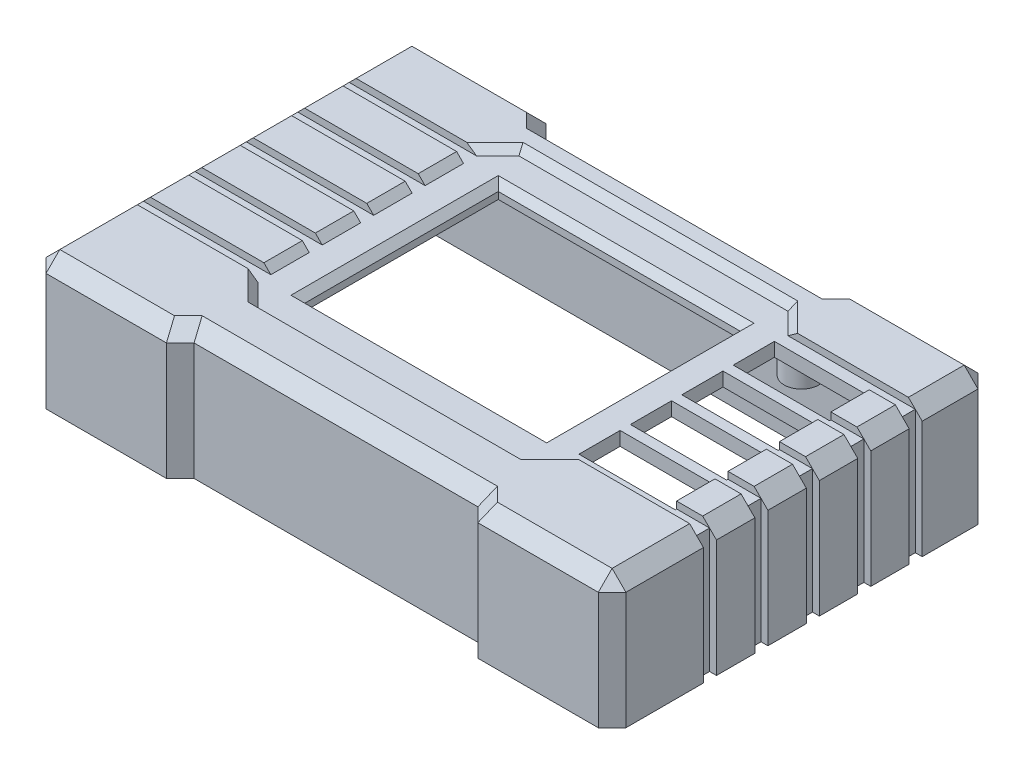
SolidWorks part; units mm, degrees
ref_plane "Спереди" through (0, 0, 0) normal (0, 0, 1) x (1, 0, 0)
ref_plane "Сверху" through (0, 0, 0) normal (0, 1, 0) x (1, 0, 0)
ref_plane "Справа" through (0, 0, 0) normal (1, 0, 0) x (0, 0, -1)
sketch "Эскиз1" plane through (0, 0, 0) normal (0, 1, 0) x (1, 0, 0)
  line L5 (-34.58, 1.516) -> (21.72, 1.516) construction
  line L6 (-37, -22.5) -> (37, -22.5)
  line L9 (-37, -22.5) -> (-37, 22.5)
  line L14 (-37, 22.5) -> (37, 22.5)
  line L15 (37, -22.5) -> (37, 22.5)
  line L20 (-37, -22.5) -> (37, 22.5) construction
  line L21 (-37, 22.5) -> (37, -22.5) construction
  line L34 (17.52, 15.531) -> (36.3729, 15.531) construction
  line L35 (26, 15) -> (32.5, 15) construction
  line L36 (-34.58, -17.984) -> (21.72, -17.984) construction
  line L37 (-34.58, -17.984) -> (-34.58, 21.016) construction
  line L38 (-34.58, 21.016) -> (21.72, 21.016) construction
  line L39 (21.72, -17.984) -> (21.72, 21.016) construction
  line L40 (-34.58, -17.984) -> (21.72, 21.016) construction
  line L41 (-34.58, 21.016) -> (21.72, -17.984) construction
  line L42 (-17.52, 15.531) -> (17.52, 15.531)
  line L47 (-17.52, 15.531) -> (-17.52, -12.499)
  line L48 (-17.52, -12.499) -> (17.52, -12.499)
  line L49 (17.52, 15.531) -> (17.52, -12.499)
  line L50 (-17.52, 15.531) -> (17.52, -12.499) construction
  line L51 (-17.52, -12.499) -> (17.52, 15.531) construction
  line L52 (-56.0698, 1.516) -> (114.5698, 1.516) construction
  line L53 (26, 15) -> (26, 10.5) construction
  line L54 (26, 10.5) -> (32.5, 10.5) construction
  line L55 (32.5, 15) -> (32.5, 10.5) construction
  line L56 (26, 7.55) -> (32.5, 7.55) construction
  line L57 (26, 7.55) -> (26, 3.05) construction
  line L58 (26, 3.05) -> (32.5, 3.05) construction
  line L59 (32.5, 7.55) -> (32.5, 3.05) construction
  line L60 (26, 0.1) -> (32.5, 0.1) construction
  line L61 (26, 0.1) -> (26, -4.4) construction
  line L62 (26, -4.4) -> (32.5, -4.4) construction
  line L63 (32.5, 0.1) -> (32.5, -4.4) construction
  line L64 (25.931, -7.35) -> (32.431, -7.35) construction
  line L65 (25.931, -7.35) -> (25.931, -11.85) construction
  line L66 (25.931, -11.85) -> (32.431, -11.85) construction
  line L67 (32.431, -7.35) -> (32.431, -11.85) construction
  line L72 (26, 15) -> (32.5, 10.5) construction
  line L74 (26, 10.5) -> (32.5, 15) construction
  line L75 (26, 0.1) -> (32.5, -4.4) construction
  line L76 (36.022, 9.969) -> (22.478, 9.969)
  line L77 (36.022, 9.969) -> (36.022, 15.531)
  line L78 (36.022, 15.531) -> (22.478, 15.531)
  line L79 (22.478, 9.969) -> (22.478, 15.531)
  line L80 (36.022, 9.969) -> (22.478, 15.531) construction
  line L81 (36.022, 15.531) -> (22.478, 9.969) construction
  line L82 (26, -4.4) -> (32.5, 0.1) construction
  line L83 (26.069, -7.35) -> (32.431, -11.85) construction
  line L84 (32.431, -7.35) -> (25.931, -11.85) construction
  line L85 (26, 7.55) -> (32.5, 3.05) construction
  line L86 (32.5, 7.55) -> (26, 3.05) construction
  line L87 (0, 22.5) -> (0, -22.5) construction
  line L88 (36.022, 2.519) -> (22.478, 2.519)
  line L89 (36.022, 2.519) -> (36.022, 8.081)
  line L90 (36.022, 8.081) -> (22.478, 8.081)
  line L91 (22.478, 2.519) -> (22.478, 8.081)
  line L92 (36.022, 2.519) -> (22.478, 8.081) construction
  line L93 (36.022, 8.081) -> (22.478, 2.519) construction
  line L94 (36.022, -4.931) -> (22.478, -4.931)
  line L95 (36.022, -4.931) -> (36.022, 0.631)
  line L96 (36.022, 0.631) -> (22.478, 0.631)
  line L97 (22.478, -4.931) -> (22.478, 0.631)
  line L98 (36.022, -4.931) -> (22.478, 0.631) construction
  line L99 (36.022, 0.631) -> (22.478, -4.931) construction
  line L100 (36.022, -12.381) -> (22.478, -12.381)
  line L101 (36.022, -12.381) -> (36.022, -6.819)
  line L102 (36.022, -6.819) -> (22.478, -6.819)
  line L103 (22.478, -12.381) -> (22.478, -6.819)
  line L104 (36.022, -12.381) -> (22.478, -6.819) construction
  line L105 (36.022, -6.819) -> (22.478, -12.381) construction
  line L106 (-36.022, -6.819) -> (-22.478, -12.381) construction
  line L107 (-36.022, -12.381) -> (-22.478, -6.819) construction
  line L108 (-36.022, 0.631) -> (-22.478, -4.931) construction
  line L109 (-36.022, -4.931) -> (-22.478, 0.631) construction
  line L110 (-36.022, 8.081) -> (-22.478, 2.519) construction
  line L111 (-36.022, 2.519) -> (-22.478, 8.081) construction
  line L112 (-32.5, 7.55) -> (-26, 3.05) construction
  line L113 (-26, 7.55) -> (-32.5, 3.05) construction
  line L114 (-32.431, -7.35) -> (-25.931, -11.85) construction
  line L115 (-26.069, -7.35) -> (-32.431, -11.85) construction
  line L116 (-26, -4.4) -> (-32.5, 0.1) construction
  line L117 (-36.022, 15.531) -> (-22.478, 9.969) construction
  line L118 (-36.022, 9.969) -> (-22.478, 15.531) construction
  line L119 (-26, 0.1) -> (-32.5, -4.4) construction
  line L120 (-26, 10.5) -> (-32.5, 15) construction
  line L121 (-26, 15) -> (-32.5, 10.5) construction
  line L122 (-32.431, -7.35) -> (-32.431, -11.85) construction
  line L123 (-25.931, -11.85) -> (-32.431, -11.85) construction
  line L124 (-25.931, -7.35) -> (-25.931, -11.85) construction
  line L125 (-25.931, -7.35) -> (-32.431, -7.35) construction
  line L126 (-32.5, 0.1) -> (-32.5, -4.4) construction
  line L127 (-26, -4.4) -> (-32.5, -4.4) construction
  line L128 (-26, 0.1) -> (-26, -4.4) construction
  line L129 (-26, 0.1) -> (-32.5, 0.1) construction
  line L130 (-32.5, 7.55) -> (-32.5, 3.05) construction
  line L131 (-26, 3.05) -> (-32.5, 3.05) construction
  line L132 (-26, 7.55) -> (-26, 3.05) construction
  line L133 (-26, 7.55) -> (-32.5, 7.55) construction
  line L134 (-32.5, 15) -> (-32.5, 10.5) construction
  line L135 (-26, 10.5) -> (-32.5, 10.5) construction
  line L136 (-26, 15) -> (-26, 10.5) construction
  line L137 (-26, 15) -> (-32.5, 15) construction
  line L138 (-22.478, -12.381) -> (-22.478, -6.819) construction
  line L139 (-36.022, -6.819) -> (-22.478, -6.819) construction
  line L140 (-36.022, -12.381) -> (-36.022, -6.819) construction
  line L141 (-36.022, -12.381) -> (-22.478, -12.381) construction
  line L142 (-22.478, -4.931) -> (-22.478, 0.631) construction
  line L143 (-36.022, 0.631) -> (-22.478, 0.631) construction
  line L144 (-36.022, -4.931) -> (-36.022, 0.631) construction
  line L145 (-36.022, -4.931) -> (-22.478, -4.931) construction
  line L146 (-22.478, 2.519) -> (-22.478, 8.081) construction
  line L147 (-36.022, 8.081) -> (-22.478, 8.081) construction
  line L148 (-36.022, 2.519) -> (-36.022, 8.081) construction
  line L149 (-36.022, 2.519) -> (-22.478, 2.519) construction
  line L150 (-22.478, 9.969) -> (-22.478, 15.531) construction
  line L151 (-36.022, 15.531) -> (-22.478, 15.531) construction
  line L152 (-36.022, 9.969) -> (-36.022, 15.531) construction
  line L153 (-36.022, 9.969) -> (-22.478, 9.969) construction
  line L154 (22.478, 15.531) -> (22.478, -16.6587) construction
  point P0 (0, 0)
  point P10 (-6.43, 1.516)
  point P17 (0, 1.516)
  point P36 (29.25, 12.75)
  point P42 (29.25, 5.3)
  point P48 (29.25, -2.15)
  point P53 (29.25, -9.6)
  point P95 (-29.25, -9.6)
  point P96 (-29.25, -2.15)
  point P97 (-29.25, 5.3)
  point P98 (-29.25, 12.75)
  dimension "D6" = 4.5
  dimension "D1" = 74
  dimension "D2" = 45
  dimension "D3" = 7.5
  dimension "D4" = 4.5
  dimension "D5" = 6.5
  dimension "D7" = 56.3
  dimension "D8" = 39
  dimension "D9" = 28.03
  dimension "D10" = 35.04
  dimension "D11" = 2.95
  dimension "D12" = 2.95
  dimension "D13" = 2.95
  dimension "D14" = 13.544
  dimension "D15" = 4.2
  dimension "D16" = 0.978
  dimension "D17" = 22.35
extrude "Бобышка-Вытянуть1" add sketch "Эскиз1" along normal blind 2
sketch "Эскиз2" plane through (-37, 0, 0) normal (-1, 0, 0) x (0, 0, 1)
  line L0 (22.5, 2) -> (22.5, 0) construction
  line L1 (-22.5, 2) -> (22.5, 2)
  line L2 (-22.5, 2) -> (-22.5, -16)
  line L3 (-22.5, -16) -> (22.5, -16)
  line L4 (22.5, 2) -> (22.5, -16)
  dimension "D1" = 18
extrude "Бобышка-Вытянуть2" add sketch "Эскиз2" along normal blind 4
sketch "Эскиз3" plane through (37, 0, 0) normal (1, 0, 0) x (0, 0, -1)
  line L1 (-22.5, 2) -> (22.5, 2)
  line L2 (-22.5, 2) -> (-22.5, -16)
  line L3 (-22.5, -16) -> (22.5, -16)
  line L4 (22.5, 2) -> (22.5, -16)
extrude "Бобышка-Вытянуть3" add sketch "Эскиз3" along normal blind 4
sketch "Эскиз4" plane through (0, 0, -22.5) normal (0, 0, -1) x (-1, 0, 0)
  line L1 (-41, 2) -> (41, 2)
  line L2 (-41, 2) -> (-41, -16)
  line L3 (-41, -16) -> (41, -16)
  line L4 (41, 2) -> (41, -16)
extrude "Бобышка-Вытянуть4" add sketch "Эскиз4" along normal blind 3
sketch "Эскиз5" plane through (0, 0, 22.5) normal (0, 0, 1) x (1, 0, 0)
  line L1 (-41, 2) -> (41, 2)
  line L2 (-41, 2) -> (-41, -16)
  line L3 (-41, -16) -> (41, -16)
  line L4 (41, 2) -> (41, -16)
extrude "Бобышка-Вытянуть5" add sketch "Эскиз5" along normal blind 3
sketch "Эскиз7" plane through (0, 2, 0) normal (0, 1, 0) x (1, 0, 0)
  line L0 (-17.52, 15.531) -> (-17.52, -12.499) construction
  line L17 (-41, -25.5) -> (-41, 25.5) construction
  line L18 (36.022, 15.531) -> (36.022, 9.969)
  line L51 (36.022, 15.531) -> (41, 15.531)
  line L52 (36.022, 9.969) -> (41, 9.969)
  line L53 (-41, -6.819) -> (-41, -12.381)
  line L54 (-22.5537, -12.381) -> (-41, -12.381)
  line L55 (-22.5537, -6.819) -> (-22.5537, -12.381)
  line L56 (-22.5537, -6.819) -> (-41, -6.819)
  line L57 (-41, 0.631) -> (-41, -4.931)
  line L58 (-22.5537, -4.931) -> (-41, -4.931)
  line L59 (-22.5537, 0.631) -> (-22.5537, -4.931)
  line L60 (-22.5537, 0.631) -> (-41, 0.631)
  line L61 (-41, 8.081) -> (-41, 2.519)
  line L62 (-22.5537, 2.519) -> (-41, 2.519)
  line L63 (-22.5537, 8.081) -> (-22.5537, 2.519)
  line L64 (-22.5537, 8.081) -> (-41, 8.081)
  line L65 (-41, 15.531) -> (-41, 9.969)
  line L66 (-22.5537, 9.969) -> (-41, 9.969)
  line L67 (-22.5537, 15.531) -> (-22.5537, 9.969)
  line L68 (-22.5537, 15.531) -> (-41, 15.531)
  line L69 (41, 15.531) -> (41, 9.969)
  line L70 (36.022, 8.081) -> (36.022, 2.519)
  line L71 (36.022, 8.081) -> (41, 8.081)
  line L72 (36.022, 2.519) -> (41, 2.519)
  line L73 (41, 8.081) -> (41, 2.519)
  line L74 (-22.5537, 15.531) -> (-22.5537, 17.419) construction
  line L75 (36.022, 2.519) -> (36.022, 8.081) construction
  line L76 (36.022, 0.631) -> (36.022, -4.931)
  line L77 (36.022, 0.631) -> (41, 0.631)
  line L78 (36.022, -4.931) -> (41, -4.931)
  line L79 (41, 0.631) -> (41, -4.931)
  line L80 (36.022, -6.819) -> (36.022, -12.381)
  line L81 (36.022, -6.819) -> (41, -6.819)
  line L82 (36.022, -12.381) -> (41, -12.381)
  line L83 (41, -6.819) -> (41, -12.381)
  line L84 (41, 25.5) -> (41, -25.5) construction
  line L85 (-41, -25.5) -> (-22.5537, -25.5)
  line L86 (-41, -25.5) -> (-41, -14.269)
  line L87 (-41, -14.269) -> (-22.5537, -14.269)
  line L88 (-22.5537, -25.5) -> (-22.5537, -14.269) construction
  line L89 (41, -25.5) -> (22.5537, -25.5)
  line L90 (41, -25.5) -> (41, -14.269)
  line L91 (41, -14.269) -> (22.5537, -14.269)
  line L92 (22.5537, -25.5) -> (22.5537, -14.269) construction
  line L97 (-41, 25.5) -> (41, 25.5) construction
  line L98 (-22.5537, 17.419) -> (-41, 17.419)
  line L115 (22.478, -2.15) -> (17.52, -2.15) construction
  line L116 (-41, 25.5) -> (-22.5537, 25.5)
  line L120 (41, 25.5) -> (22.5537, 25.5)
  line L124 (-22.5537, -25.5) -> (22.5537, -25.5)
  line L125 (-22.5537, -25.5) -> (-22.5537, -17.457) construction
  line L126 (-22.5537, -17.457) -> (22.5537, -17.457) construction
  line L127 (22.5537, -25.5) -> (22.5537, -17.457) construction
  line L128 (22.478, 0.631) -> (22.478, -4.931) construction
  line L129 (17.52, -12.499) -> (17.52, 15.531) construction
  line L130 (0, -12.499) -> (0, -17.457) construction
  line L131 (-17.52, -12.499) -> (17.52, -12.499) construction
  line L132 (-22.5537, -14.269) -> (-19.3657, -17.457)
  line L133 (22.5537, -14.269) -> (19.3657, -17.457)
  line L134 (-19.3657, -17.457) -> (19.3657, -17.457)
  line L135 (36.022, -6.819) -> (22.478, -6.819) construction
  line L136 (-22.5537, -12.381) -> (-22.5537, -14.269) construction
  line L137 (-22.5537, 20.489) -> (22.5537, 20.489) construction
  line L138 (-10.3983, 20.489) -> (-10.3983, 15.531) construction
  line L139 (17.52, 15.531) -> (-17.52, 15.531) construction
  line L142 (-22.5537, 25.5) -> (22.5537, 25.5)
  line L144 (-41, 25.5) -> (-41, 17.419)
  line L145 (41, 25.5) -> (41, 17.419)
  line L146 (41, 17.419) -> (22.5537, 17.419)
  line L147 (-22.5537, 17.419) -> (-19.4836, 20.489)
  line L148 (22.5537, 17.419) -> (19.4836, 20.489)
  line L150 (-22.5537, 17.419) -> (-22.5537, 25.5) construction
  line L151 (22.5537, 17.419) -> (22.5537, 25.5) construction
  line L152 (-19.4836, 20.489) -> (19.4836, 20.489)
  line L153 (36.022, 15.531) -> (22.478, 15.531) construction
  line L154 (22.478, 9.969) -> (36.022, 9.969) construction
  line L155 (36.022, 8.081) -> (22.478, 8.081) construction
  line L156 (22.478, 2.519) -> (36.022, 2.519) construction
  line L157 (36.022, 0.631) -> (22.478, 0.631) construction
  line L158 (22.478, -4.931) -> (36.022, -4.931) construction
  line L161 (22.478, -12.381) -> (36.022, -12.381) construction
  line L162 (-22.5537, 9.969) -> (-22.5537, 8.081) construction
  dimension "D1" = 5.0337
  dimension "D2" = 45
  dimension "D3" = 45
  dimension "D4" = 5.562
  dimension "D5" = 45
  dimension "D6" = 45
extrude "Бобышка-Вытянуть6" add sketch "Эскиз7" along normal blind 1
sketch "Эскиз8" plane through (-41, 0, 0) normal (-1, 0, 0) x (0, 0, 1)
  line L0 (-25.5, -16) -> (25.5, -16) construction
  line L1 (-15.531, 3) -> (-9.969, 3)
  line L2 (-15.531, 3) -> (-15.531, -16)
  line L3 (-15.531, -16) -> (-9.969, -16)
  line L4 (-9.969, 3) -> (-9.969, -16)
  line L5 (-15.531, 3) -> (-9.969, 3) construction
  line L6 (14.269, 3) -> (25.5, 3)
  line L7 (-8.081, 3) -> (-2.519, 3)
  line L8 (-8.081, 3) -> (-8.081, -16)
  line L9 (-8.081, -16) -> (-2.519, -16)
  line L10 (-2.519, 3) -> (-2.519, -16)
  line L11 (-0.631, 3) -> (4.931, 3)
  line L12 (-0.631, 3) -> (-0.631, -16)
  line L13 (-0.631, -16) -> (4.931, -16)
  line L14 (4.931, 3) -> (4.931, -16)
  line L15 (6.819, 3) -> (12.381, 3)
  line L16 (6.819, 3) -> (6.819, -16)
  line L17 (6.819, -16) -> (12.381, -16)
  line L18 (12.381, 3) -> (12.381, -16)
  line L19 (14.269, 3) -> (14.269, -16)
  line L20 (25.5, 3) -> (25.5, -16)
  line L21 (14.269, -16) -> (25.5, -16)
  line L26 (-17.419, 3) -> (-25.5, 3)
  line L27 (-17.419, 3) -> (-17.419, -16)
  line L28 (-25.5, 3) -> (-25.5, -16)
  line L29 (-17.419, -16) -> (-25.5, -16)
  line L30 (25.5, -16) -> (-25.5, -16) construction
extrude "Бобышка-Вытянуть7" add sketch "Эскиз8" along normal blind 1
sketch "Эскиз9" plane through (41, 0, 0) normal (1, 0, 0) x (0, 0, -1)
  line L0 (-25.5, -16) -> (25.5, -16) construction
  line L1 (-12.381, 3) -> (-6.819, 3)
  line L2 (-12.381, 3) -> (-12.381, -16)
  line L3 (-12.381, -16) -> (-6.819, -16)
  line L4 (-6.819, 3) -> (-6.819, -16)
  line L5 (-12.381, 3) -> (-6.819, 3) construction
  line L6 (-14.269, 3) -> (-25.5, 3)
  line L7 (-4.931, 3) -> (0.631, 3)
  line L8 (-4.931, 3) -> (-4.931, -16)
  line L9 (-4.931, -16) -> (0.631, -16)
  line L10 (0.631, 3) -> (0.631, -16)
  line L11 (2.519, 3) -> (8.081, 3)
  line L12 (2.519, 3) -> (2.519, -16)
  line L13 (2.519, -16) -> (8.081, -16)
  line L14 (8.081, 3) -> (8.081, -16)
  line L15 (9.969, 3) -> (15.531, 3)
  line L16 (9.969, 3) -> (9.969, -16)
  line L17 (9.969, -16) -> (15.531, -16)
  line L18 (15.531, 3) -> (15.531, -16)
  line L19 (-14.269, 3) -> (-14.269, -16)
  line L20 (-25.5, 3) -> (-25.5, -16)
  line L21 (-14.269, -16) -> (-25.5, -16)
  line L26 (17.419, 3) -> (25.5, 3)
  line L27 (17.419, 3) -> (17.419, -16)
  line L28 (25.5, 3) -> (25.5, -16)
  line L29 (17.419, -16) -> (25.5, -16)
extrude "Бобышка-Вытянуть8" add sketch "Эскиз9" along normal blind 1
sketch "Эскиз11" plane through (0, 3, 0) normal (0, 1, 0) x (1, 0, 0)
  line L0 (-42, 25.5) -> (-42, 27.5)
  line L1 (-42, -25.5) -> (-42, -27.5)
  line L2 (42, 25.5) -> (42, 27.5)
  line L3 (42, -25.5) -> (42, -27.5)
  line L4 (42, -27.5) -> (22.5537, -27.5)
  line L5 (-42, -27.5) -> (-22.5537, -27.5)
  line L7 (-42, 27.5) -> (-22.5537, 27.5)
  line L8 (42, 27.5) -> (22.5537, 27.5)
  line L10 (-42, 17.419) -> (-42, 25.5) construction
  line L11 (-22.5537, 17.419) -> (-22.5537, 27.5) construction
  line L13 (42, 25.5) -> (-42, 25.5) construction
  line L14 (-22.5537, 27.5) -> (-20.5537, 25.5)
  line L15 (-20.5537, 25.5) -> (-42, 25.5)
  line L17 (22.5537, 27.5) -> (20.5537, 25.5)
  line L20 (42, 25.5) -> (20.5537, 25.5)
  line L21 (-22.5537, -27.5) -> (-20.5537, -25.5)
  line L22 (-42, -25.5) -> (42, -25.5) construction
  line L23 (-20.5537, -25.5) -> (-42, -25.5)
  line L24 (22.5537, -27.5) -> (20.5537, -25.5)
  line L25 (20.5537, -25.5) -> (42, -25.5)
  dimension "D1" = 2
  dimension "D2" = 45
  dimension "D3" = 45
  dimension "D4" = 45
  dimension "D5" = 45
extrude "Бобышка-Вытянуть9" add sketch "Эскиз11" against normal up to vertex (19 mm away) up to point (42, -16, 25.5)
chamfer "Фаска15" distance 2 angle 45 26 edges at (42, 3, -12.75) (42, 3, -5.3) (42, 3, 2.15) (42, 3, 9.6) (42, 3, 20.8845) (42, -6.5, 27.5) (32.2768, 3, 27.5) (21.5537, 3, 26.5) (0, 3, 25.5) (-21.5537, 3, 26.5) (-32.2768, 3, 27.5) (-42, -6.5, 27.5) (-42, 3, 20.8845) (-42, 3, 9.6) (-42, 3, 2.15) (-42, 3, -5.3) (-42, 3, -12.75) (42, -6.5, -27.5) (42, 3, -22.4595) (32.2768, 3, -27.5) (21.5537, 3, -26.5) (0, 3, -25.5) (-21.5537, 3, -26.5) (-42, 3, -22.4595) (-32.2768, 3, -27.5) (-42, -6.5, -27.5)
chamfer "Фаска16" distance 1 angle 45 10 edges at (20.9597, 3, 15.863) (0, 3, 17.457) (-20.9597, 3, 15.863) (-22.5537, 3, 9.6) (-22.5537, 3, 2.15) (-22.5537, 3, -5.3) (-22.5537, 3, -12.75) (21.0187, 3, -18.954) (0, 3, -20.489) (-21.0187, 3, -18.954)
sketch "Эскиз12" plane through (0, 0, 0) normal (0, -1, 0) x (1, 0, 0)
  line L0 (-17.52, 12.499) -> (17.52, -15.531) construction
  line L1 (-17.52, 12.499) -> (17.52, 12.499) construction
  line L2 (-17.52, 12.499) -> (-17.52, -15.531) construction
  line L3 (-17.52, -15.531) -> (17.52, -15.531) construction
  line L4 (17.52, 12.499) -> (17.52, -15.531) construction
  line L5 (17.52, 12.499) -> (-17.52, -15.531) construction
  line L6 (-17.52, -1.516) -> (17.52, -1.516) construction
  line L7 (-30.78, 17.984) -> (25.52, 17.984) construction
  line L8 (-30.78, 17.984) -> (-30.78, -21.016) construction
  line L9 (-30.78, -21.016) -> (25.52, -21.016) construction
  line L10 (25.52, 17.984) -> (25.52, -21.016) construction
  line L11 (-30.78, 17.984) -> (25.52, -21.016) construction
  line L12 (25.52, 17.984) -> (-30.78, -21.016) construction
  line L13 (0, 0) -> (0, -1.516) construction
  line L14 (23.22, -18.716) -> (-28.48, -18.716) construction
  line L15 (23.22, -18.716) -> (23.22, 15.684) construction
  line L16 (23.22, 15.684) -> (-28.48, 15.684) construction
  line L17 (-28.48, -18.716) -> (-28.48, 15.684) construction
  line L18 (23.22, -18.716) -> (-28.48, 15.684) construction
  line L19 (23.22, 15.684) -> (-28.48, -18.716) construction
  line L20 (20.35, -18.516) -> (-25.698, -18.516) construction
  line L21 (20.35, -18.516) -> (20.35, 15.484) construction
  line L22 (20.35, 15.484) -> (-25.698, 15.484) construction
  line L23 (-25.698, -18.516) -> (-25.698, 15.484) construction
  line L24 (20.35, -18.516) -> (-25.698, 15.484) construction
  line L25 (20.35, 15.484) -> (-25.698, -18.516) construction
  circle A0 centre (-28.48, 15.684) radius 0.9
  circle A1 centre (-28.48, 15.684) radius 2.5
  circle A2 centre (23.22, 15.684) radius 0.9
  circle A3 centre (23.22, 15.684) radius 2.5
  circle A4 centre (-28.48, -18.716) radius 0.9
  circle A5 centre (-28.48, -18.716) radius 2.5
  circle A6 centre (23.22, -18.716) radius 0.9
  circle A7 centre (23.22, -18.716) radius 2.5
  point P12 (25.52, -1.516)
  point P13 (-2.63, -1.516)
  point P26 (-2.674, -1.516)
  dimension "D6" = 1.8
  dimension "D7" = 5
  dimension "D8" = 2.83
  dimension "D1" = 56.3
  dimension "D2" = 39
  dimension "D3" = 8
  dimension "D4" = 34.4
  dimension "D5" = 51.7
  dimension "D9" = 34
  dimension "D10" = 1.516
extrude "Бобышка-Вытянуть10" add sketch "Эскиз12" along normal blind 3.25
sketch "Эскиз13" plane through (0, 0, 0) normal (0, -1, 0) x (1, 0, 0)
  line L0 (0, 22.5) -> (0, 0) construction
  line L1 (-37, 22.5) -> (37, 22.5) construction
  line L2 (-37, 22.5) -> (-37, -22.5) construction
  line L3 (-37, -22.5) -> (37, -22.5) construction
  line L4 (37, 22.5) -> (37, -22.5) construction
  line L5 (0, -1.75) -> (0, 0) construction
  line L6 (-33, -18.5) -> (33, -18.5) construction
  line L7 (-33, -18.5) -> (-33, 15) construction
  line L8 (-33, 15) -> (33, 15) construction
  line L9 (33, -18.5) -> (33, 15) construction
  line L10 (-33, -18.5) -> (33, 15) construction
  line L11 (-33, 15) -> (33, -18.5) construction
  line L14 (-37, -19.5) -> (-37, -22.5)
  line L16 (-37, -22.5) -> (-34, -22.5)
  line L17 (-37, 22.5) -> (-34, 22.5)
  line L18 (-37, 22.5) -> (-37, 19.5)
  line L19 (37, -22.5) -> (34, -22.5)
  line L20 (37, -19.5) -> (37, -22.5)
  line L21 (37, 22.5) -> (34, 22.5)
  line L22 (37, 22.5) -> (37, 19.5)
  circle A0 centre (-33, -18.5) radius 1 construction
  circle A1 centre (-33, -18.5) radius 2 construction
  circle A2 centre (33, -18.5) radius 1 construction
  circle A3 centre (33, -18.5) radius 2 construction
  circle A4 centre (-33, 15) radius 1 construction
  circle A5 centre (-33, 15) radius 2 construction
  circle A6 centre (33, 15) radius 1 construction
  circle A7 centre (33, 15) radius 2 construction
  circle A10 centre (-37, -22.5) radius 1 construction
  circle A12 centre (-37, -22.5) radius 3 construction
  arc A13 (-37, -19.5) -> (-34, -22.5) centre (-37, -22.5) cw
  arc A15 (-34, 22.5) -> (-37, 19.5) centre (-37, 22.5) cw
  arc A16 (37, -19.5) -> (34, -22.5) centre (37, -22.5) ccw
  arc A17 (34, 22.5) -> (37, 19.5) centre (37, 22.5) ccw
  point P9 (0, -1.75)
  dimension "D4" = 2
  dimension "D5" = 4
  dimension "D6" = 6
  dimension "D7" = 2
  dimension "D8" = 1.75
  dimension "D1" = 4
  dimension "D2" = 33.5
  dimension "D3" = 66
extrude "Бобышка-Вытянуть11" add sketch "Эскиз13" along normal up to vertex (16 mm away) up to point (-37, -16, -22.5)
sketch "Эскиз15" plane through (0, -16, 0) normal (0, -1, 0) x (1, 0, 0)
  line L0 (-37, -19.5) -> (-37, -22.5) construction
  line L1 (-34, -22.5) -> (-37, -22.5) construction
  line L2 (-37, 19.5) -> (-37, 22.5) construction
  line L3 (-34, 22.5) -> (-37, 22.5) construction
  line L4 (0, 22.5) -> (0, -22.5) construction
  line L5 (-34, 22.5) -> (34, 22.5) construction
  line L6 (34, -22.5) -> (-34, -22.5) construction
  line L7 (34, -22.5) -> (37, -22.5) construction
  line L8 (37, -22.5) -> (37, -19.5) construction
  line L9 (34, 22.5) -> (37, 22.5) construction
  line L10 (37, 22.5) -> (37, 19.5) construction
  circle A0 centre (-37, -22.5) radius 0.9
  arc A1 (-37, 19.5) -> (-34, 22.5) centre (-37, 22.5) ccw construction
  circle A2 centre (-37, 22.5) radius 0.9
  circle A3 centre (37, -22.5) radius 0.9
  circle A4 centre (37, 22.5) radius 0.9
  dimension "D1" = 1.8
extrude "Вырез-Вытянуть1" cut sketch "Эскиз15" against normal up to surface (16 mm away) up to face at (23.22, 0, -21.216)
sketch "Эскиз16" plane through (-37, 0, 0) normal (1, 0, 0) x (0, 0, -1)
  line L0 (19.5, -16) -> (19.5, 0) construction
  line L1 (13.4, -8.5313) -> (13.4, -16) construction
  line L2 (19.5, -8.5313) -> (13.4, -8.5313) construction
  line L3 (19.5, -16) -> (-19.5, -16) construction
  circle A0 centre (13.4, -16) radius 1.6
  dimension "D3" = 3.2
  dimension "D1" = 6.1
  dimension "D2" = 7.4687
extrude "Вырез-Вытянуть3" cut sketch "Эскиз16" against normal through all
sketch "Эскиз17" plane through (-37, 0, 0) normal (1, 0, 0) x (0, 0, -1)
  line L6 (10.37, -16) -> (2.37, -16) construction
  line L7 (9.87, -15.3) -> (2.87, -15.3) construction
  line L8 (10.37, -16) -> (10.37, -15.8) construction
  line L9 (10.37, -15.8) -> (9.87, -15.3) construction
  line L10 (2.87, -15.3) -> (2.37, -15.8) construction
  line L11 (2.37, -15.8) -> (2.37, -16) construction
  line L12 (11.8, -16) -> (-19.5, -16) construction
  line L13 (2.27, -16) -> (2.27, -15.7586)
  line L14 (0.631, -16) -> (2.519, -16) construction
  line L15 (2.27, -15.7586) -> (2.8286, -15.2)
  line L16 (2.8286, -15.2) -> (9.9114, -15.2)
  line L17 (9.9114, -15.2) -> (10.47, -15.7586)
  line L18 (10.47, -15.7586) -> (10.47, -16)
  line L19 (9.969, -16) -> (15.531, -16) construction
  line L21 (2.27, -16) -> (10.47, -16)
  dimension "D2" = 9.13
  dimension "D3" = 0.1
  dimension "D4" = 0.1
  dimension "D5" = 0.1
  dimension "D6" = 0.1
  dimension "D7" = 45
  dimension "D8" = 8
  dimension "D9" = 7
  dimension "D10" = 0.7
  dimension "D11" = 0.1
extrude "Вырез-Вытянуть4" cut sketch "Эскиз17" against normal through all
sketch "Эскиз18" plane through (-42, 0, 0) normal (-1, 0, 0) x (0, 0, 1)
  line L0 (-17.419, -16) -> (-17.419, -13.4)
  line L1 (-17.419, -16) -> (-17.419, 1) construction
  line L2 (-0.631, -13.4) -> (-0.631, -16)
  line L3 (-0.631, 2) -> (-0.631, -16) construction
  line L4 (-1.631, -12.4) -> (-16.419, -12.4)
  line L5 (-17.419, -16) -> (-0.631, -16)
  line L6 (-17.419, -16) -> (-17.419, 2) construction
  line L7 (-25.5, -16) -> (-17.419, -16) construction
  line L8 (-13.4, -14.4) -> (-13.4, -16) construction
  line L9 (-17.419, -13.4) -> (-16.419, -12.4)
  line L10 (-0.631, -13.4) -> (-1.631, -12.4)
  arc A4 (-11.8, -16) -> (-15, -16) centre (-13.4, -16) ccw construction
  point P1 (-17.419, -12.4)
  point P5 (-0.631, -12.4)
  dimension "D1" = 2
extrude "Вырез-Вытянуть5" cut sketch "Эскиз18" against normal blind 2.5
chamfer "Фаска17" distance 1 angle 45 4 edges at (0, 2, 12.499) (-17.52, 2, -1.516) (17.52, 2, -1.516) (0, 2, -15.531)
sketch "Эскиз19" plane through (0, 3, 0) normal (0, 1, 0) x (1, 0, 0)
  line L0 (22.478, 15.531) -> (36.022, 9.969) construction
  line L1 (22.478, 15.531) -> (36.022, 15.531) construction
  line L2 (22.478, 15.531) -> (22.478, 9.969) construction
  line L3 (22.478, 9.969) -> (36.022, 9.969) construction
  line L4 (36.022, 15.531) -> (36.022, 9.969) construction
  line L5 (22.478, 8.081) -> (36.022, 8.081) construction
  line L6 (22.478, 8.081) -> (22.478, 2.519) construction
  line L7 (22.478, 2.519) -> (36.022, 2.519) construction
  line L8 (36.022, 8.081) -> (36.022, 2.519) construction
  line L9 (22.478, 0.631) -> (36.022, 0.631) construction
  line L10 (22.478, 0.631) -> (22.478, -4.931) construction
  line L11 (22.478, -4.931) -> (36.022, -4.931) construction
  line L12 (36.022, 0.631) -> (36.022, -4.931) construction
  line L13 (22.478, -6.819) -> (36.022, -6.819) construction
  line L14 (22.478, -6.819) -> (22.478, -12.381) construction
  line L15 (22.478, -12.381) -> (36.022, -12.381) construction
  line L16 (36.022, -6.819) -> (36.022, -12.381) construction
  line L17 (36.022, 15.531) -> (22.478, 9.969) construction
  line L18 (22.478, 8.081) -> (36.022, 2.519) construction
  line L19 (36.022, 8.081) -> (22.478, 2.519) construction
  line L20 (22.478, 0.631) -> (36.022, -4.931) construction
  line L21 (36.022, 0.631) -> (22.478, -4.931) construction
  line L22 (22.478, -6.819) -> (36.022, -12.381) construction
  line L23 (36.022, -6.819) -> (22.478, -12.381) construction
  line L25 (36.222, 9.769) -> (22.278, 9.769)
  line L26 (36.222, 9.769) -> (36.222, 15.731)
  line L27 (36.222, 15.731) -> (22.278, 15.731)
  line L28 (22.278, 9.769) -> (22.278, 15.731)
  line L29 (36.222, 9.769) -> (22.278, 15.731) construction
  line L30 (36.222, 15.731) -> (22.278, 9.769) construction
  line L31 (36.222, 2.319) -> (22.278, 2.319)
  line L32 (36.222, 2.319) -> (36.222, 8.281)
  line L33 (36.222, 8.281) -> (22.278, 8.281)
  line L34 (22.278, 2.319) -> (22.278, 8.281)
  line L35 (36.222, 2.319) -> (22.278, 8.281) construction
  line L36 (36.222, 8.281) -> (22.278, 2.319) construction
  line L37 (36.222, -5.131) -> (22.278, -5.131)
  line L38 (36.222, -5.131) -> (36.222, 0.831)
  line L39 (36.222, 0.831) -> (22.278, 0.831)
  line L40 (22.278, -5.131) -> (22.278, 0.831)
  line L41 (36.222, -5.131) -> (22.278, 0.831) construction
  line L42 (36.222, 0.831) -> (22.278, -5.131) construction
  line L43 (36.222, -6.619) -> (22.278, -6.619)
  line L44 (36.222, -6.619) -> (36.222, -12.581)
  line L45 (36.222, -12.581) -> (22.278, -12.581)
  line L46 (22.278, -6.619) -> (22.278, -12.581)
  line L47 (36.222, -6.619) -> (22.278, -12.581) construction
  line L48 (36.222, -12.581) -> (22.278, -6.619) construction
  point P24 (29.25, 12.75)
  point P29 (29.25, 5.3)
  point P34 (29.25, -2.15)
  point P39 (29.25, -9.6)
  dimension "D1" = 0.2
  dimension "D2" = 0.2
extrude "Вырез-Вытянуть6" cut sketch "Эскиз19" against normal up to surface (3 mm away) up to face at (23.22, 0, -21.216)
sketch "Эскиз20" plane through (0, 0, 22.5) normal (0, 0, -1) x (-1, 0, 0)
  line L0 (-34, 0) -> (-34, -16) construction
  line L1 (-34, -8) -> (34, -8) construction
  line L2 (34, -16) -> (34, 0) construction
  circle A0 centre (-30, -8) radius 3.2
  circle A1 centre (30, -8) radius 3.2
  dimension "D1" = 6.4
  dimension "D3" = 4
  dimension "D2" = 4
extrude "Вырез-Вытянуть7" cut sketch "Эскиз20" against normal blind 2.2
chamfer "Фаска18" distance 1 angle 45 2 edges at (-42, -12.4, -5.3) (-42, -12.4, -12.75)
